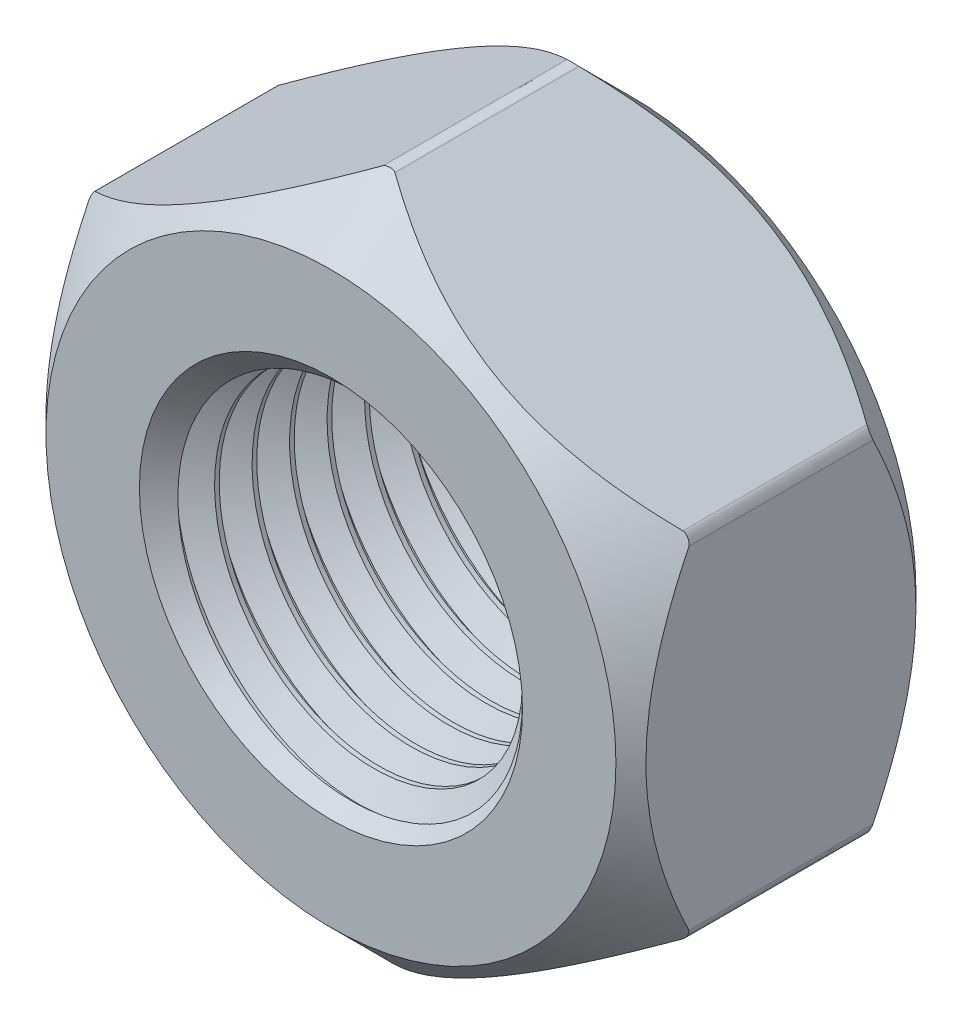
SolidWorks part; units mm, degrees
ref_plane "Front Plane" through (0, 0, 0) normal (0, 0, 1) x (1, 0, 0)
ref_plane "Top Plane" through (0, 0, 0) normal (0, 1, 0) x (1, 0, 0)
ref_plane "Right Plane" through (0, 0, 0) normal (1, 0, 0) x (0, 0, -1)
sketch "Sketch1" plane through (0, 0, 0) normal (0, 0, 1) x (1, 0, 0)
  line L0 (0, 4.6188) -> (0, -4.6188) construction
  line L1 (0, -4.6188) -> (4, -2.3094) construction
  line L2 (4, -2.3094) -> (4, 2.3094) construction
  line L3 (4, 2.3094) -> (0, 4.6188) construction
  line L4 (0, 4.6188) -> (-4, 2.3094) construction
  line L5 (-4, 2.3094) -> (-4, -2.3094) construction
  line L6 (-4, -2.3094) -> (0, -4.6188) construction
  line L7 (-4, 0) -> (4, 0) construction
  line L8 (0, 0) -> (-1.25, -2.1651) construction
  circle A0 centre (0, 0) radius 4 construction
  circle A1 centre (0, 0) radius 2.5 construction
  point P12 (0, 0)
  point P13 (0, -2.5)
  point P16 (2.5, 0)
  point P17 (0, 2.5)
  point P18 (-2.5, 0)
  point P20 (-1.25, -2.1651)
  dimension "Thread Diameter" = 5
  dimension "Width" = 8
  dimension "D1" = 30
sketch "Sketch2" plane through (0, 0, 0) normal (1, 0, 0) x (0, 0, -1)
  line L0 (-2, 0) -> (2, 0) construction
  line L1 (-2, 2.5) -> (2, 2.5) construction
  line L2 (-2, -2.5) -> (2, -2.5) construction
  line L3 (-2, 4) -> (2, 4) construction
  line L4 (-2, -4) -> (2, -4) construction
  line L13 (2, -4) -> (2, 4) construction
  line L14 (-2, 4) -> (-2, -4) construction
  line L15 (-2.4687, 2.5541) -> (-1.9688, 2.5541) construction
  line L16 (-1.9688, 2.5541) -> (-2.2187, 2.1211) construction
  line L17 (-2.2187, 2.1211) -> (-2.4687, 2.5541) construction
  line L18 (-2.4531, 2.5271) -> (-1.9844, 2.5271) construction
  line L19 (-2.4375, 2.5) -> (-2, 2.5) construction
  line L20 (-2.25, 2.1752) -> (-2.1875, 2.1752) construction
  line L21 (-2.2187, 2.1752) -> (-2.2187, 2.1211) construction
  line L22 (-2.2188, 2.5) -> (-2.2188, 2.5541) construction
  point P2 (0, 0)
  point P5 (-2, 0)
  point P6 (2, 0)
  point P14 (0, 4)
  point P15 (0, -2.5)
  point P18 (0, 2.5)
  point P23 (0, -4)
  point P35 (-2.2188, 2.5271)
  dimension "Height" = 4
  dimension "Thread Pitch" = 0.5
  dimension "D2" = 0.0625
sketch "Sketch3" plane through (0, 0, 0) normal (0, 0, 1) x (1, 0, 0)
  line L0 (-4, 0) -> (4, 0) construction
  line L1 (0, -4.6188) -> (4, -2.3094)
  line L2 (4, -2.3094) -> (4, 2.3094)
  line L3 (4, 2.3094) -> (0, 4.6188)
  line L4 (0, 4.6188) -> (-4, 2.3094)
  line L5 (-4, 2.3094) -> (-4, -2.3094)
  line L6 (-4, -2.3094) -> (0, -4.6188)
  circle A0 centre (0, 0) radius 4 construction
  circle A1 centre (0, 0) radius 2.5 construction
  circle A2 centre (0, 0) radius 2.5 construction
  circle A3 centre (0, 0) radius 2.1752
extrude "Boss-Extrude1" add sketch "Sketch3" along normal up to vertex (2 mm away) and the other way up to vertex (2 mm away) up to point (0, 0, 2) other way up to point (0, 0, -2)
sketch "Sketch4" plane through (0, 0, 0) normal (0, 0, 1) x (1, 0, 0)
  circle A1 centre (0, 0) radius 3.8
  dimension "D1" = 7.6
extrude "Cut-Extrude1" cut sketch "Sketch4" against normal through all draft 45 from vertex flip side to cut starting at point (0, 0, 2)
extrude "Cut-Extrude2" cut sketch "Sketch4<2>" along normal through all draft 45 from vertex flip side to cut starting at point (0, 0, -2)
sketch "Sketch4<2>" plane through (0, 0, 0) normal (0, 0, 1) x (1, 0, 0) same geometry as "Sketch4"
chamfer "Chamfer1" distance 0.3125 angle 45 2 edges at (2.1752, 0, -2) (2.1752, 0, 2)
fillet "Fillet1" radius 0.16 6 edges at (-4, 2.3094, 0) (-4, -2.3094, 0) (0, -4.6188, 0) (4, -2.3094, 0) (4, 2.3094, 0) (0, 4.6188, 0) conic rho 0.3
sketch "Sketch5" plane through (0, 0, 0) normal (0, 0, 1) x (1, 0, 0)
  circle A0 centre (0, 0) radius 2.5 construction
  circle A1 centre (0, 0) radius 2.5
extrude "Cut-Extrude3" cut sketch "Sketch5" against normal through all both and the other way through all
sketch "Sketch7" plane through (0, 0, 2) normal (0, 0, 1) x (1, 0, 0)
  circle A0 centre (0, 0) radius 2.5 construction
  circle A1 centre (0, 0) radius 2.5
curve "Helix/Spiral1" pitch 0.5 height 4.5 radius 2.5 centre (0, 0, 2) axis (0, 0, -1) start towards (0, 1, 0)
sketch "Sketch8" plane through (0, 0, 0) normal (1, 0, 0) x (0, 0, -1)
  line L0 (-2.4531, 2.5271) -> (-1.9844, 2.5271)
  line L1 (-1.9844, 2.5271) -> (-2.1875, 2.1752)
  line L2 (-2.1875, 2.1752) -> (-2.25, 2.1752)
  line L3 (-2.25, 2.1752) -> (-2.4531, 2.5271)
sweep "Sweep1" add profiles "Sketch8" path "Helix/Spiral1"
sketch "Sketch9" plane through (0, 0, 2) normal (0, 0, 1) x (1, 0, 0)
  circle A0 centre (0, 0) radius 2.5541
extrude "Cut-Extrude4" cut sketch "Sketch9" against normal through all draft 45 and the other way through all
sketch "Sketch10" plane through (0, 0, -2) normal (0, 0, -1) x (-1, 0, 0)
  circle A1 centre (0, 0) radius 2.5541
  circle A2 centre (0, 0) radius 2.5541
  dimension "D1" = 0
extrude "Cut-Extrude5" cut sketch "Sketch10" against normal through all draft 45 and the other way through all
equation "\"D2@Sketch2\" = \"Thread Pitch@Sketch2\" / 8"
equation "\"D1@Sketch4\"=\"Width@Sketch1\"*.95"
equation "\"D1@Chamfer1\" = \"Thread Pitch@Sketch2\" * .625"
equation "\"D1@Fillet1\"=\"Width@Sketch1\"*.02"
equation "\"D3@Helix/Spiral1\" = \"Height@Sketch2\" + \"Thread Pitch@Sketch2\""
equation "\"D4@Helix/Spiral1\" = \"Thread Pitch@Sketch2\""
